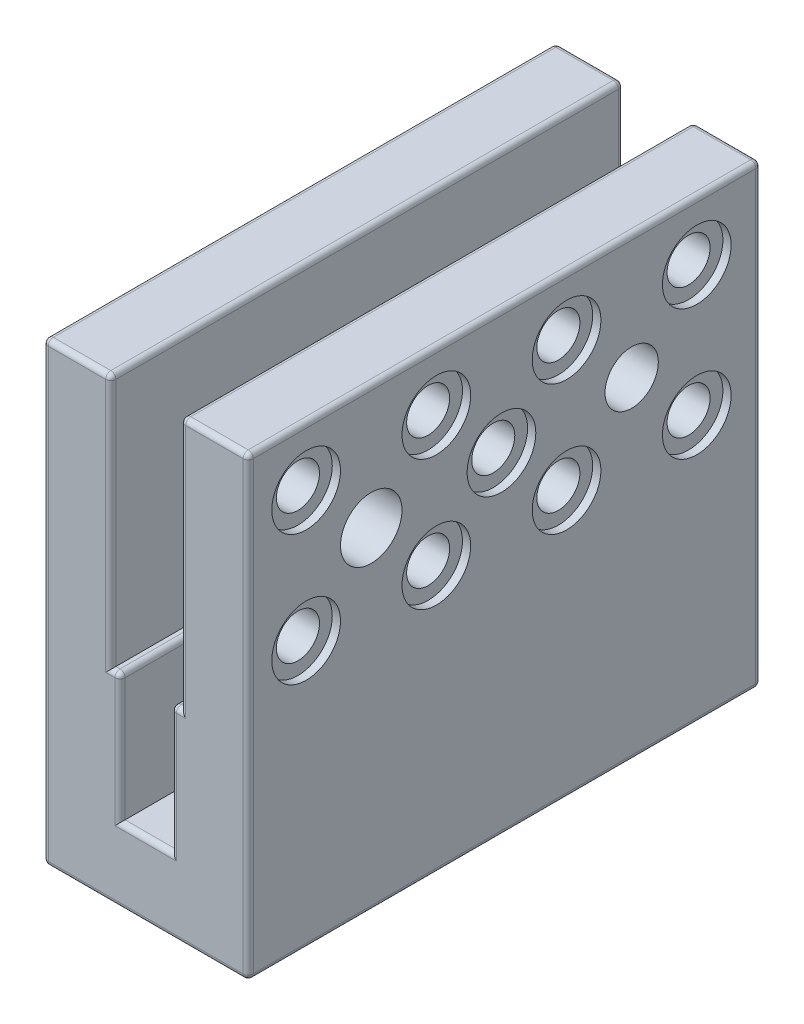
SolidWorks part; units mm, degrees
ref_plane "Front Plane" through (0, 0, 0) normal (0, 0, 1) x (1, 0, 0)
ref_plane "Top Plane" through (0, 0, 0) normal (0, 1, 0) x (1, 0, 0)
ref_plane "Right Plane" through (0, 0, 0) normal (1, 0, 0) x (0, 0, -1)
sketch "Sketch2" plane through (0, 0, 0) normal (0, 1, 0) x (1, 0, 0)
  line L1 (-10, 25) -> (10, 25)
  line L2 (-10, 25) -> (-10, -25)
  line L3 (-10, -25) -> (10, -25)
  line L4 (10, 25) -> (10, -25)
  line L5 (-10, 25) -> (10, -25) construction
  line L6 (-10, -25) -> (10, 25) construction
  point P1 (0, 0)
  dimension "D1" = 20
  dimension "D2" = 50
extrude "Boss-Extrude1" add sketch "Sketch2" along normal blind 44.5
sketch "Sketch3" plane through (0, 0, 25) normal (0, 0, 1) x (1, 0, 0)
  line L0 (-10, 44.5) -> (10, 44.5) construction
  line L1 (-3.4, 44.5) -> (3.4, 44.5)
  line L2 (-3.4, 44.5) -> (-3.4, 19.75)
  line L3 (-3.4, 19.75) -> (3.4, 19.75)
  line L4 (3.4, 44.5) -> (3.4, 19.75)
  line L7 (-2.5, 7.25) -> (2.5, 7.25)
  line L8 (-2.5, 7.25) -> (-2.5, 19.75)
  line L9 (-2.5, 19.75) -> (2.5, 19.75)
  line L10 (2.5, 7.25) -> (2.5, 19.75)
  point P8 (0, 19.75)
  point P12 (0, 19.75)
  dimension "D1" = 6.8
  dimension "D2" = 24.75
  dimension "D3" = 5
  dimension "D4" = 12.5
extrude "Cut-Extrude3" cut sketch "Sketch3" against normal through all contours L10 L9 L8 L7 | L2 L3 L4 L1
sketch "Sketch4" plane through (10, 0, 0) normal (1, 0, 0) x (0, 0, -1)
  line L0 (-25, 0) -> (25, 0) construction
  line L1 (-25, 44.5) -> (-25, 19.75) construction
  line L2 (-13, 32.41) -> (21.4534, 32.41) construction
  line L3 (-19.35, 38.76) -> (21.4534, 38.76) construction
  circle A0 centre (-13, 32.41) radius 3
  circle A7 centre (-0.3, 32.41) radius 2.1
  circle A8 centre (12.4, 32.41) radius 2.6
  circle A9 centre (-19.35, 38.76) radius 2.1
  circle A10 centre (-6.65, 38.76) radius 2.1
  circle A11 centre (6.05, 38.76) radius 2.1
  circle A12 centre (18.75, 38.76) radius 2.1
  circle A13 centre (18.75, 26.06) radius 2.1
  circle A14 centre (6.05, 26.06) radius 2.1
  circle A15 centre (-6.65, 26.06) radius 2.1
  circle A16 centre (-19.35, 26.06) radius 2.1
  dimension "D3" = 6
  dimension "D6" = 4.2
  dimension "D7" = 5.2
  dimension "D10" = 4.2
  dimension "D11" = 4.2
  dimension "D12" = 4.2
  dimension "D16" = 4.2
  dimension "D1" = 32.41
  dimension "D2" = 12
  dimension "D4" = 12.7
  dimension "D5" = 12.7
  dimension "D8" = 6.35
  dimension "D9" = 6.35
  dimension "D13" = 12.7
  dimension "D14" = 12.7
  dimension "D15" = 12.7
extrude "Cut-Extrude4" cut sketch "Sketch4" against normal through all contours A8 | A0
extrude "Cut-Extrude5" cut sketch "Sketch4<3>" against normal up to next contours A10 | A9 | A13 | A12 | A14 | A11 | A15 | A16 | A7
sketch "Sketch4<3>" plane through (10, 0, 0) normal (1, 0, 0) x (0, 0, -1) same geometry as "Sketch4"
sketch "Sketch5" plane through (-10, 0, 0) normal (-1, 0, 0) x (0, 0, 1)
  circle A0 centre (13, 32.41) radius 2.6
  circle A1 centre (13, 32.41) radius 3
  dimension "D1" = 5.2
  dimension "D2" = 6
extrude "Boss-Extrude2" add sketch "Sketch5" against normal blind 6.6
sketch "Sketch6" plane through (3.4, 0, 0) normal (-1, 0, 0) x (0, 0, 1)
  circle A0 centre (-18.75, 26.06) radius 3.1
  circle A1 centre (-18.75, 38.76) radius 3.1
  circle A2 centre (-6.05, 38.76) radius 3.1
  circle A3 centre (6.65, 38.76) radius 3.1
  circle A4 centre (0.3, 32.41) radius 3.1
  circle A5 centre (-6.05, 26.06) radius 3.1
  circle A6 centre (6.65, 26.06) radius 3.1
  circle A7 centre (19.35, 26.06) radius 3.1
  circle A8 centre (19.35, 38.76) radius 3.1
  dimension "D1" = 6.2
extrude "Cut-Extrude6" cut sketch "Sketch6" against normal blind 1.23
sketch "Sketch7" plane through (-10, 0, 0) normal (-1, 0, 0) x (0, 0, 1)
  line L0 (-25, 0) -> (25, 0) construction
  line L1 (-18.6, 3.48) -> (-14, 3.48)
  line L2 (-18.6, 3.48) -> (-18.6, 23.58)
  line L3 (-18.6, 23.58) -> (-14, 23.58)
  line L4 (-14, 3.48) -> (-14, 23.58)
  line L5 (-25, 44.5) -> (-25, 0) construction
  dimension "D1" = 3.48
  dimension "D2" = 20.1
  dimension "D3" = 4.6
  dimension "D4" = 6.4
extrude "Cut-Extrude7" cut sketch "Sketch7" against normal blind 3.25
fillet "Fillet1" radius 0.5 32 edges at (-10, 0, 0) (10, 0, 0) (-10, 22.25, -25) (0, 0, -25) (10, 22.25, -25) (3.4, 32.125, -25) (2.95, 19.75, -25) (2.5, 13.5, -25) (0, 7.25, -25) (-2.5, 13.5, -25) (-2.95, 19.75, -25) (-3.4, 32.125, -25) (-2.5, 13.5, 25) (0, 7.25, 25) (2.5, 13.5, 25) (2.95, 19.75, 25) (3.4, 32.125, 25) (10, 22.25, 25) (0, 0, 25) (-10, 22.25, 25) (-3.4, 32.125, 25) (-2.95, 19.75, 25) (10, 44.5, 0) (6.7, 44.5, 25) (3.4, 44.5, 0) (6.7, 44.5, -25) (-6.7, 44.5, 25) (-10, 44.5, 0) (-6.7, 44.5, -25) (-3.4, 44.5, 0) (2.5, 19.75, 0) (-2.5, 19.75, 0)
sketch "Sketch8" plane through (10, 0, 0) normal (1, 0, 0) x (0, 0, -1)
  circle A0 centre (-19.35, 38.76) radius 3.35
  circle A1 centre (-6.65, 38.76) radius 3.35
  circle A2 centre (6.05, 38.76) radius 3.35
  circle A3 centre (18.75, 38.76) radius 3.35
  circle A4 centre (-0.3, 32.41) radius 3.35
  circle A5 centre (-19.35, 26.06) radius 3.35
  circle A6 centre (-6.65, 26.06) radius 3.35
  circle A7 centre (6.05, 26.06) radius 3.35
  circle A8 centre (18.75, 26.06) radius 3.35
  dimension "D1" = 6.7
extrude "Cut-Extrude8" cut sketch "Sketch8" against normal blind 0.8
